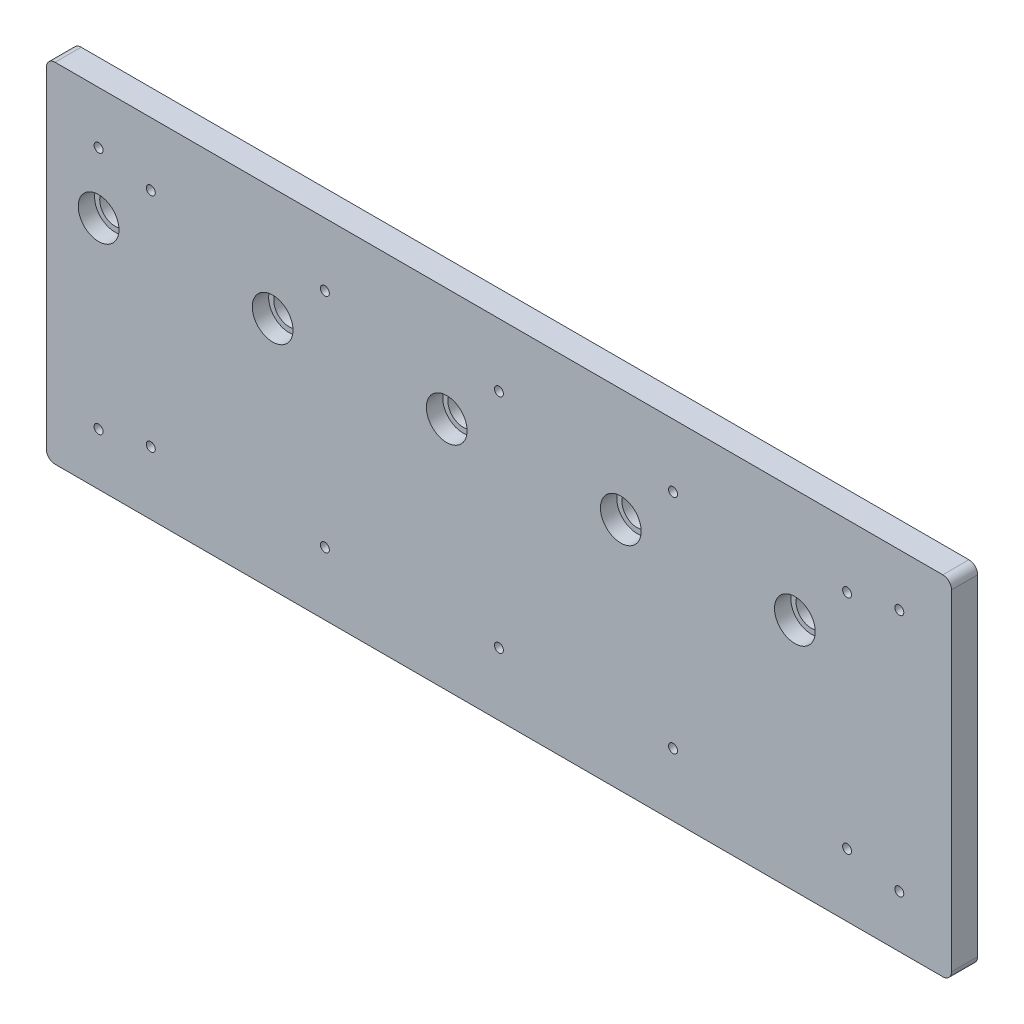
SolidWorks part; units mm, degrees
ref_plane "Front Plane" through (0, 0, 0) normal (0, 0, 1) x (1, 0, 0)
ref_plane "Top Plane" through (0, 0, 0) normal (0, 1, 0) x (1, 0, 0)
ref_plane "Right Plane" through (0, 0, 0) normal (1, 0, 0) x (0, 0, -1)
sketch "Sketch2" plane through (0, 0, 0) normal (0, 0, 1) x (1, 0, 0)
  line L1 (-330.2, -127) -> (330.2, -127)
  line L2 (-330.2, -127) -> (-330.2, 127)
  line L3 (-330.2, 127) -> (330.2, 127)
  line L4 (330.2, -127) -> (330.2, 127)
  line L5 (-330.2, -127) -> (330.2, 127) construction
  line L6 (-330.2, 127) -> (330.2, -127) construction
  point P0 (0, 0)
  dimension "D1" = 660.4
  dimension "D2" = 254
extrude "Boss-Extrude1" add sketch "Sketch2" along normal blind 19.05
hole_wizard "1/4 Clearance Hole1" positions "Sketch3" profile "Sketch4" hole size "1/4" standard "ANSI Inch" end condition up to next
sketch "Sketch3" plane through (0, 0, 19.05) normal (0, 0, 1) x (1, 0, 0)
  line L9 (330.2, -127) -> (330.2, 127) construction
  line L10 (330.2, 127) -> (-330.2, 127) construction
  line L11 (-330.2, 127) -> (330.2, -127) construction
  point P121 (-254, 81.026)
  point P129 (-127, 81.026)
  point P130 (0, 81.026)
  point P131 (127, 81.026)
  point P132 (254, 81.026)
  point P133 (-127, -81.026)
  point P134 (0, -81.026)
  point P135 (127, -81.026)
  point P136 (254, -81.026)
  point P137 (-254, -81.026)
  dimension "D1" = 81.026
  dimension "D2" = 254
sketch "Sketch4" plane through (-254, -81.026, 19.05) normal (1, 0, 0) x (0, -1, 0)
  line L0 (0, 0) -> (0, 19.05)
  line L1 (0, 19.05) -> (3.2639, 19.05)
  line L2 (3.2639, 19.05) -> (3.2639, 0)
  line L5 (3.2639, 0) -> (0, 0)
  line L11 (0, -6.35) -> (0, 107.95) construction
  dimension "Thru Hole Dia." = 6.5278
  dimension "Thru Hole Depth" = 19.05
fillet "Fillet1" radius 6.35 4 edges at (330.2, 127, 9.525) (330.2, -127, 9.525) (-330.2, -127, 9.525) (-330.2, 127, 9.525)
hole_wizard "1/4 Clearance Hole2" positions "Sketch5" profile "Sketch7" hole size "1/4" standard "ANSI Inch" end condition through all
sketch "Sketch5" plane through (0, 0, 19.05) normal (0, 0, 1) x (1, 0, 0)
  line L3 (-292.1, 88.9) -> (292.1, 88.9) construction
  line L4 (-292.1, 88.9) -> (-292.1, -88.9) construction
  line L5 (-292.1, -88.9) -> (292.1, -88.9) construction
  line L6 (292.1, 88.9) -> (292.1, -88.9) construction
  line L7 (323.85, 127) -> (-323.85, 127) construction
  line L8 (-330.2, 120.65) -> (-330.2, -120.65) construction
  line L9 (-323.85, -127) -> (323.85, -127) construction
  line L10 (330.2, -120.65) -> (330.2, 120.65) construction
  point P0 (-292.1, 88.9)
  point P16 (292.1, -88.9)
  point P77 (-292.1, -88.9)
  point P78 (292.1, 88.9)
  dimension "D1" = 38.1
  dimension "D2" = 38.1
  dimension "D3" = 38.1
  dimension "D4" = 38.1
sketch "Sketch7" plane through (-292.1, 88.9, 19.05) normal (1, 0, 0) x (0, -1, 0)
  line L0 (0, 0) -> (0, 19.05)
  line L1 (0, 19.05) -> (3.2639, 19.05)
  line L2 (3.2639, 19.05) -> (3.2639, 0)
  line L5 (3.2639, 0) -> (0, 0)
  line L11 (0, -6.35) -> (0, 107.95) construction
  dimension "Thru Hole Dia." = 6.5278
  dimension "Thru Hole Depth" = 19.05
sketch "Sketch10" plane through (0, 0, 0) normal (0, 0, -1) x (-1, 0, 0)
  line L0 (-330.2, -120.65) -> (-330.2, 120.65) construction
  line L1 (-323.85, 127) -> (323.85, 127) construction
  circle A0 centre (-215.9, 44.45) radius 11.1125
  circle A1 centre (-88.9, 44.45) radius 11.1125
  circle A2 centre (38.1, 44.45) radius 11.1125
  circle A3 centre (165.1, 44.45) radius 11.1125
  circle A4 centre (292.1, 44.45) radius 11.1125
  dimension "D1" = 114.3
  dimension "D2" = 82.55
  dimension "D3" = 22.225
  dimension "D4" = 5
extrude "Cut-Extrude1" cut sketch "Sketch10" against normal through all
sketch "Sketch12" plane through (0, 0, 19.05) normal (0, 0, 1) x (1, 0, 0)
  circle A0 centre (-292.1, 44.45) radius 14.859
  circle A1 centre (-165.1, 44.45) radius 14.859
  circle A2 centre (-38.1, 44.45) radius 14.859
  circle A3 centre (88.9, 44.45) radius 14.859
  circle A4 centre (215.9, 44.45) radius 14.859
  dimension "D1" = 29.718
  dimension "D2" = 5
extrude "Cut-Extrude2" cut sketch "Sketch12" against normal blind 11.938
